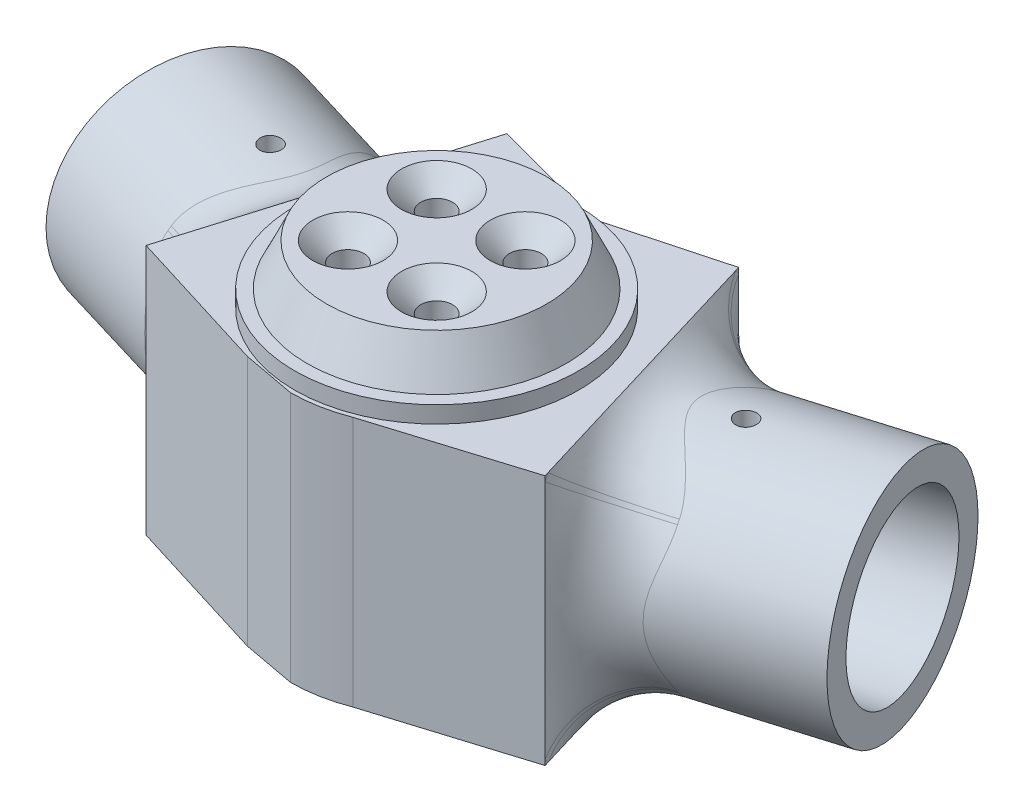
SolidWorks part; units mm, degrees
ref_plane "Alzado" through (0, 0, 0) normal (0, 0, 1) x (1, 0, 0)
ref_plane "Planta" through (0, 0, 0) normal (0, 1, 0) x (1, 0, 0)
ref_plane "Vista lateral" through (0, 0, 0) normal (1, 0, 0) x (0, 0, -1)
sketch "Croquis1" plane through (0, 0, 0) normal (0, 1, 0) x (1, 0, 0)
  circle A0 centre (0, 0) radius 17
  dimension "D1" = 34
extrude "Saliente-Extruir1" add sketch "Croquis1" along normal blind 32
ref_plane "Plano1" through (0, 32, 0) normal (0, 1, 0) x (1, 0, 0)
sketch "Croquis2" plane through (0, 32, 0) normal (0, 1, 0) x (1, 0, 0)
  circle A0 centre (0, 0) radius 15.5
  dimension "D1" = 31
ref_plane "Plano2" through (0, 37, 0) normal (0, 1, 0) x (1, 0, 0)
sketch "Croquis3" plane through (0, 37, 0) normal (0, 1, 0) x (1, 0, 0)
  circle A0 centre (0, 0) radius 13.1685
  dimension "D1" = 26.337
loft "Recubrir1" add profiles "Croquis2", "Croquis3" connector at (0, 32, 15.5) connector at (0, 37, 13.1685)
sketch "Croquis4" plane through (0, 37, 0) normal (0, 1, 0) x (1, 0, 0)
  line L0 (-13.1685, 0) -> (13.1685, 0) construction
  line L1 (0, 13.1685) -> (0, -13.1685) construction
  line L2 (0, 0) -> (5.3033, 5.3033) construction
  line L3 (0, 0) -> (-5.3033, 5.3033) construction
  line L4 (-5.3033, 5.3033) -> (5.3033, -5.3033) construction
  line L5 (5.3033, -5.3033) -> (0, 0) construction
  line L6 (0, 0) -> (-5.3033, -5.3033) construction
  circle A0 centre (0, 0) radius 13.1685 construction
  circle A1 centre (0, 0) radius 13.1685 construction
  circle A2 centre (5.3033, 5.3033) radius 4.2
  circle A3 centre (-5.3033, 5.3033) radius 4.2
  circle A4 centre (-5.3033, -5.3033) radius 4.2
  circle A5 centre (5.3033, -5.3033) radius 4.2
  dimension "D1" = 8.4
  dimension "D2" = 7.5
  dimension "D3" = 7.5
  dimension "D4" = 7.5
extrude "Cortar-Extruir1" cut sketch "Croquis4" against normal blind 2.3
sketch "Croquis5" plane through (0, 34.7, 0) normal (0, 1, 0) x (1, 0, 0)
  circle A0 centre (-5.3033, 5.3033) radius 1.9
  circle A1 centre (5.3033, 5.3033) radius 1.9
  circle A2 centre (5.3033, -5.3033) radius 1.9
  circle A3 centre (-5.3033, -5.3033) radius 1.9
  dimension "D1" = 3.8
extrude "Cortar-Extruir2" cut sketch "Croquis5" against normal through all
chamfer "Chaflán1" distance 2.3 angle 45 4 edges at (-5.3033, 34.7, 9.5033) (-5.3033, 34.7, -1.1033) (5.3033, 34.7, 9.5033) (5.3033, 34.7, -1.1033)
sketch "Croquis12" plane through (0, 0, 0) normal (0, -1, 0) x (1, 0, 0)
  line L0 (0, 17.5) -> (-6.3168, 16.3202)
  line L1 (-6.3168, 16.3202) -> (-23.847, 10.8911)
  line L2 (-23.847, 10.8911) -> (-13.8503, -22.259)
  line L4 (0, -18.51) -> (-13.8503, -22.259)
  line L5 (0, -17) -> (0, -18.51) construction
  line L6 (0, -18.51) -> (13.8503, -22.259)
  line L7 (23.847, 10.8911) -> (13.8503, -22.259)
  line L8 (6.3168, 16.3202) -> (23.847, 10.8911)
  arc A0 (6.3168, 16.3202) -> (-6.3168, 16.3202) centre (0, 0) ccw
  circle A1 centre (0, 0) radius 17 construction
  circle M17 centre (0, 0) radius 17
  dimension "D1" = 35
  dimension "D2" = 6.426
  dimension "D3" = 1.51
  dimension "D4" = 19.687
  dimension "D5" = 19.687
extrude "Saliente-Extruir2" add sketch "Croquis12" against normal blind 30 contours L6 L7 L8 A0 L0 L1 L2 L4 M17 region at (3.2016, 0, 17.1415)
sketch "Croquis13" plane through (18.8486, 0, -5.684) normal (0.9574, 0, -0.2887) x (-0.2887, 0, -0.9574)
  line L0 (0, 0) -> (0, 30) construction
  line L1 (-17.3123, 30) -> (17.3123, 30) construction
  circle A0 centre (0, 15) radius 13.5
  circle A1 centre (0, 15) radius 10.1
  dimension "D1" = 27
  dimension "D2" = 20.2
extrude "Saliente-Extruir3" add sketch "Croquis13" along normal blind 25
sketch "Croquis14" plane through (-18.8486, 0, -5.684) normal (-0.9574, 0, -0.2887) x (-0.2887, 0, 0.9574)
  line L0 (0, 0) -> (0, 30) construction
  line L1 (17.3123, 30) -> (-17.3123, 30) construction
  circle A0 centre (0, 15) radius 13.5
  circle A1 centre (0, 15) radius 10.1
  dimension "D1" = 27
  dimension "D2" = 20.2
extrude "Saliente-Extruir4" add sketch "Croquis14" along normal blind 25
fillet "Redondeo2" radius 9 2 edges at (-22.7463, 15, 7.2411) (22.7463, 15, 7.2411)
sketch "Croquis15" plane through (0, 0, 0) normal (0, -1, 0) x (1, 0, 0)
  circle A0 centre (0, 0) radius 12.5
  dimension "D1" = 25
extrude "Cortar-Extruir3" cut sketch "Croquis15" against normal blind 24
sketch "Croquis17" plane through (0, 37, 0) normal (0, 1, 0) x (1, 0, 0)
  line L0 (0, 0) -> (-54.4268, 0) construction
  line L1 (-42.784, 12.9019) -> (-42.784, 0) construction
  line L2 (-39.868, 22.5717) -> (-45.7, 3.232) construction
  line L3 (-42.784, 12.9019) -> (0, 0) construction
  line L4 (0, 0) -> (42.784, 12.9019) construction
  line L5 (45.7, 3.232) -> (39.868, 22.5717) construction
  line L6 (42.784, 12.9019) -> (42.784, 0) construction
  line L7 (42.784, 0) -> (0, 0) construction
  circle A0 centre (-28.4228, 8.5711) radius 1.25
  circle A1 centre (28.4228, 8.5711) radius 1.25
  dimension "D1" = 2.5
  dimension "D2" = 2.5
  dimension "D3" = 15
  dimension "D4" = 15
extrude "Cortar-Extruir4" cut sketch "Croquis17" against normal through all
